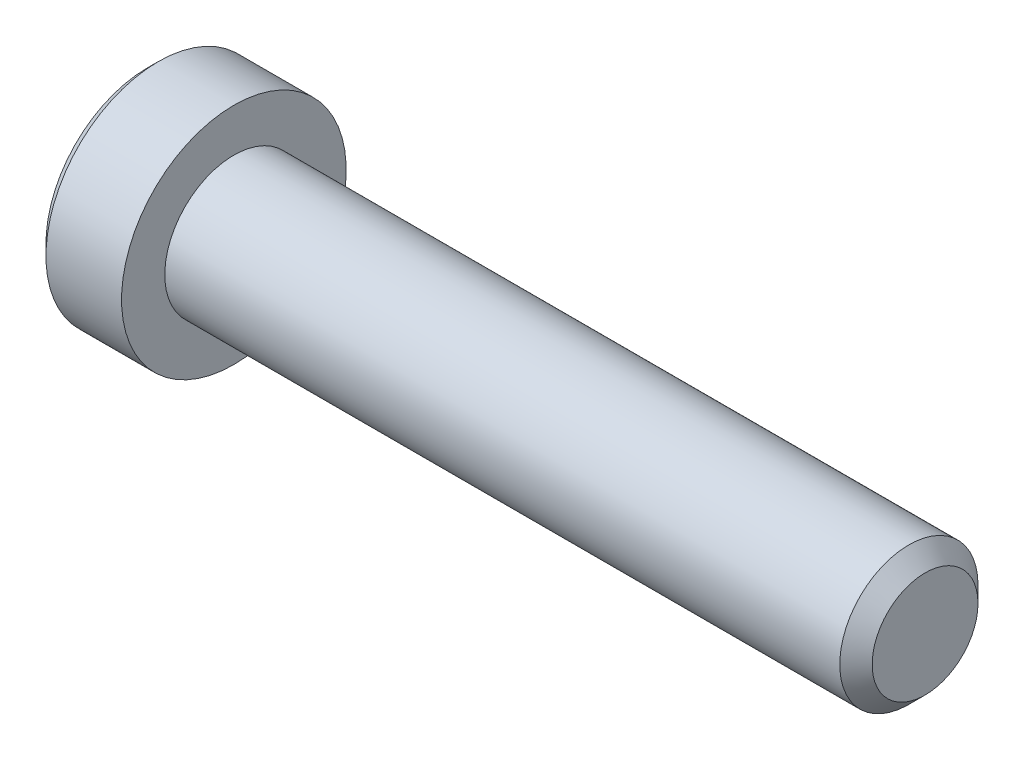
SolidWorks part; units mm, degrees
ref_plane "Front Plane" through (0, 0, 0) normal (0, 0, 1) x (1, 0, 0)
ref_plane "Top Plane" through (0, 0, 0) normal (0, 1, 0) x (1, 0, 0)
ref_plane "Right Plane" through (0, 0, 0) normal (1, 0, 0) x (0, 0, -1)
sketch "Sketch1" plane through (0, 0, 0) normal (0, 0, 1) x (1, 0, 0)
  line L0 (20, 0) -> (-20, 0) construction
  line L1 (20, 4) -> (20, -4) construction
  line L2 (-20, 6.5) -> (-20, -6.5) construction
  line L3 (-20, 6.5) -> (-24.375, 6.5) construction
  line L4 (-24.375, 6.5) -> (-25, 5.875) construction
  line L5 (-25, 5.875) -> (-25, -5.875) construction
  line L6 (-25, -5.875) -> (-24.375, -6.5) construction
  line L7 (-24.375, -6.5) -> (-20, -6.5) construction
  line L8 (-2, 4) -> (-2, -4) construction
  point P7 (-21.05, 0)
  point P12 (15, -4)
  dimension "D1" = 45
  dimension "Dec." = 8
  dimension "Length" = 40
  dimension "Head Dia" = 13
  dimension "Head Height" = 5
  dimension "Hex Depth" = 3.95
  dimension "Chamfer" = 0.625
  dimension "D2" = 5
  dimension "Thread Length" = 22
ref_plane "Plane1" through (20, 0, 0) normal (1, 0, 0) x (0, 0, -1)
ref_plane "Plane2" through (-25, 0, 0) normal (1, 0, 0) x (0, 0, -1)
sketch "Sketch2" plane through (20, 0, 0) normal (1, 0, 0) x (0, 0, -1)
  circle A0 centre (0, 0) radius 4
extrude "Boss-Extrude1" add sketch "Sketch2" against normal up to vertex (22 mm away) up to point (-2, 4, 0)
sketch "Sketch3" plane through (20, 0, 0) normal (1, 0, 0) x (0, 0, -1)
  circle A0 centre (0, 0) radius 4 construction
  circle A1 centre (0, 0) radius 4
curve "Helix/Spiral1" pitch 1.25 height 23.25 turns 18.6 parameters "Pitch"=1.25
chamfer "Chamfer1" distance 0.9375 angle 45 1 edges at (20, 0, -4)
sketch "Sketch5" plane through (0, 0, 0) normal (0, 0, 1) x (1, 0, 0)
  line L0 (19.4531, 4) -> (20.5469, 4)
  line L1 (20.5469, 4) -> (20.0781, 3.1881)
  line L2 (20.0781, 3.1881) -> (19.9219, 3.1881)
  line L3 (19.9219, 3.1881) -> (19.4531, 4)
  line L4 (20, 3.1881) -> (20, 4) construction
  line L5 (19.6875, 3.5941) -> (20.3125, 3.5941) construction
  dimension "D1" = 60
  dimension "D2" = 0.625
  dimension "D3" = 0.1562
sweep "Cut-Sweep1" [suppressed] cut profiles "Sketch5" path "Helix/Spiral1"
sketch "Sketch4" plane through (-25, 0, 0) normal (1, 0, 0) x (0, 0, -1)
  line L0 (-6.5, 0.7937) -> (6.5, 0.7937) construction
  line L1 (0, 2.8868) -> (-2.5, 1.4434)
  line L2 (-2.5, 1.4434) -> (-2.5, -1.4434)
  line L3 (-2.5, -1.4434) -> (0, -2.8868)
  line L4 (0, -2.8868) -> (2.5, -1.4434)
  line L5 (2.5, -1.4434) -> (2.5, 1.4434)
  line L6 (2.5, 1.4434) -> (0, 2.8868)
  line L7 (0, 0) -> (0, 0.7937) construction
  circle A0 centre (0, 0) radius 2.5 construction
  dimension "Hex Size" = 5
  dimension "D1" = 13
  dimension "D2" = 0.7937
sketch "Sketch10" plane through (0, 0, 0) normal (0, 0, 1) x (1, 0, 0)
  line L0 (-20, 0) -> (0.3094, 0) construction
  line L1 (0.3094, 0) -> (-2, 4)
  line L2 (-2, 4) -> (-20, 4)
  line L3 (-20, 4) -> (-20, 0)
  line L4 (-20, 6.5) -> (-20, -6.5) construction
  line L5 (-20, 0) -> (0.3094, 0)
  dimension "D1" = 60
revolve "Revolve2" add sketch "Sketch10" angle 360 about L0
sketch "Sketch6" plane through (0, 0, 0) normal (0, 0, 1) x (1, 0, 0)
  line L0 (-24.375, 6.5) -> (-25, 5.875) construction
  line L1 (-20, 6.5) -> (-24.375, 6.5) construction
  line L2 (-20, 6.5) -> (-20, -6.5) construction
  line L3 (-25, 5.875) -> (-25, -5.875) construction
  line L4 (-24.375, 6.5) -> (-25, 5.875)
  line L5 (-20, 6.5) -> (-24.375, 6.5)
  line L6 (-20, 6.5) -> (-20, 0)
  line L7 (-25, 5.875) -> (-25, 0)
  line L8 (-20, 0) -> (-25, 0) construction
  line L9 (-20, 0) -> (-25, 0)
revolve "Revolve1" add sketch "Sketch6" angle 360 about L8
extrude "Cut-Extrude1" cut sketch "Sketch4" along normal up to vertex (3.95 mm away) up to point (-21.05, 0, 0)
sketch "Sketch8" plane through (-25, 0, 0) normal (-1, 0, 0) x (0, 0, 1)
  circle A1 centre (0, 0) radius 2.8868
extrude "Cut-Extrude2" cut sketch "Sketch8" against normal through all draft 45
equation "\"D3@Helix/Spiral1\" = \"Thread Length@Sketch1\"+\"Pitch@Helix/Spiral1\""
equation "\"D3@Sketch5\" = \"Pitch@Helix/Spiral1\"*.125"
equation "\"D2@Sketch5\" = \"Pitch@Helix/Spiral1\"*.50"
equation "\"D1@Chamfer1\" = \"Pitch@Helix/Spiral1\"*.75"
equation "\"D2@Sketch1\" = \"Pitch@Helix/Spiral1\"*4"
equation "\"D1@Sketch4\" = \"Head Dia@Sketch1\""
equation "\"Chamfer@Sketch1\" = \"Head Height@Sketch1\"/8"
